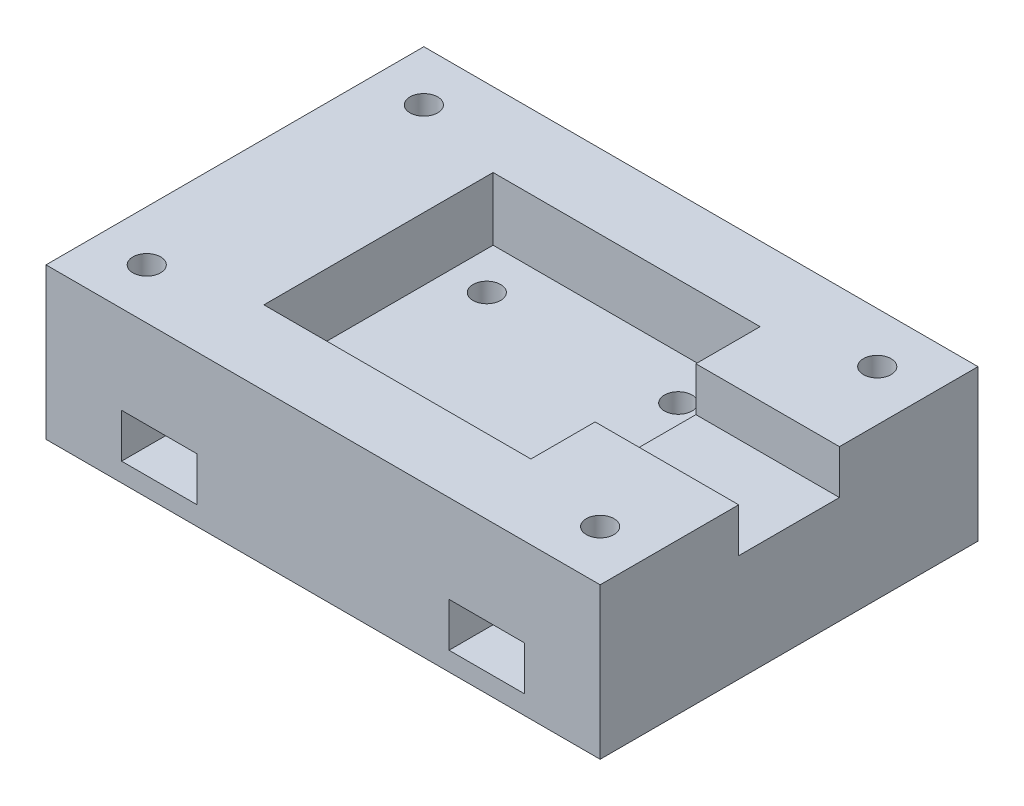
SolidWorks part; units mm, degrees
ref_plane "Front Plane" through (0, 0, 0) normal (0, 0, 1) x (1, 0, 0)
ref_plane "Top Plane" through (0, 0, 0) normal (0, 1, 0) x (1, 0, 0)
ref_plane "Right Plane" through (0, 0, 0) normal (1, 0, 0) x (0, 0, -1)
sketch "Sketch1" plane through (0, 0, 0) normal (0, 1, 0) x (1, 0, 0)
  line L1 (-22, -15) -> (22, -15)
  line L2 (-22, -15) -> (-22, 15)
  line L3 (-22, 15) -> (22, 15)
  line L4 (22, -15) -> (22, 15)
  line L5 (-22, -15) -> (22, 15) construction
  line L6 (-22, 15) -> (22, -15) construction
  point P0 (0, 0)
  dimension "D1" = 44
  dimension "D2" = 30
extrude "Pod Body" add sketch "Sketch1" along normal blind 12
ref_plane "Pod Top" through (0, 12, 0) normal (0, 1, 0) x (1, 0, 0)
sketch "Sketch2" plane through (0, 12, 0) normal (0, 1, 0) x (1, 0, 0)
  line L1 (-10.6, -9.1) -> (10.6, -9.1)
  line L2 (-10.6, -9.1) -> (-10.6, 9.1)
  line L3 (-10.6, 9.1) -> (10.6, 9.1)
  line L4 (10.6, -9.1) -> (10.6, 9.1)
  line L5 (-10.6, -9.1) -> (10.6, 9.1) construction
  line L6 (-10.6, 9.1) -> (10.6, -9.1) construction
  point P0 (0, 0)
  dimension "D1" = 21.2
  dimension "D2" = 18.2
extrude "Board Pocket" cut sketch "Sketch2" against normal blind 5
sketch "Sketch3" plane through (0, 12, 0) normal (0, 1, 0) x (1, 0, 0)
  circle A0 centre (-7.6, 5.6) radius 1.1
  circle A1 centre (7.6, 5.6) radius 1.1
extrude "Board Pilot Holes" cut sketch "Sketch3" against normal blind 9
sketch "Sketch4" plane through (0, 12, 0) normal (0, 1, 0) x (1, 0, 0)
  circle A0 centre (-18, -11) radius 1.1
  circle A1 centre (-18, 11) radius 1.1
  circle A2 centre (18, -11) radius 1.1
  circle A3 centre (18, 11) radius 1.1
extrude "Lid Pilot Holes" cut sketch "Sketch4" against normal blind 6
sketch "Sketch5" plane through (0, 12, 0) normal (0, 1, 0) x (1, 0, 0)
  line L1 (10.35, -4) -> (23, -4)
  line L2 (10.35, -4) -> (10.35, 4)
  line L3 (10.35, 4) -> (23, 4)
  line L4 (23, -4) -> (23, 4)
extrude "Cable Exit" cut sketch "Sketch5" against normal blind 3.5
sketch "Sketch7" plane through (0, 0, 0) normal (0, 0, 1) x (1, 0, 0)
  line L0 (-12, 5) -> (-6, 5) construction
  line L1 (-16, 1.5) -> (-10, 1.5)
  line L2 (-16, 1.5) -> (-16, 5)
  line L3 (-16, 5) -> (-10, 5)
  line L4 (-10, 1.5) -> (-10, 5)
  line L5 (6, 1.5) -> (12, 1.5) construction
  line L6 (10, 1.5) -> (16, 1.5)
  line L7 (10, 1.5) -> (10, 5)
  line L8 (10, 5) -> (16, 5)
  line L9 (16, 1.5) -> (16, 5)
extrude "Strap Slots" cut sketch "Sketch7" against normal through all and the other way through all
equation "\"PodL\"= 44.0"
equation "\"PodW\"= 30.0"
equation "\"PodH\"= 12.0"
equation "\"BoardL\"= 20.0"
equation "\"BoardW\"= 17.0"
equation "\"Clear\"= 0.6"
equation "\"PocketD\"= 5.0"
equation "\"D1@Sketch1\" = \"PodL\""
equation "\"D2@Sketch1\" = \"PodW\""
equation "\"HoleSpacing\"= 15.2"
equation "\"HoleOffset\"= 5.6"
equation "\"PilotD\"= 2.2"
equation "\"FloorHoleD\"= 4.0"
equation "\"LidInset\"= 4.0"
equation "\"StrapX\"= 13.0"
equation "\"StrapW\"= 6.0"
equation "\"StrapT\"= 3.5"
equation "\"StrapZ0\"= 1.5"
equation "\"CableW\"= 8.0"
equation "\"D1@Pod Top\" = \"PodH\""
equation "\"D1@Sketch2\" = \"BoardL\" + 2 * \"Clear\""
equation "\"D2@Sketch2\" = \"BoardW\" + 2 * \"Clear\""
equation "\"D1@Board Pocket\" = \"PocketD\""
equation "\"D1@Board Pilot Holes\" = \"PocketD\" + \"FloorHoleD\""
